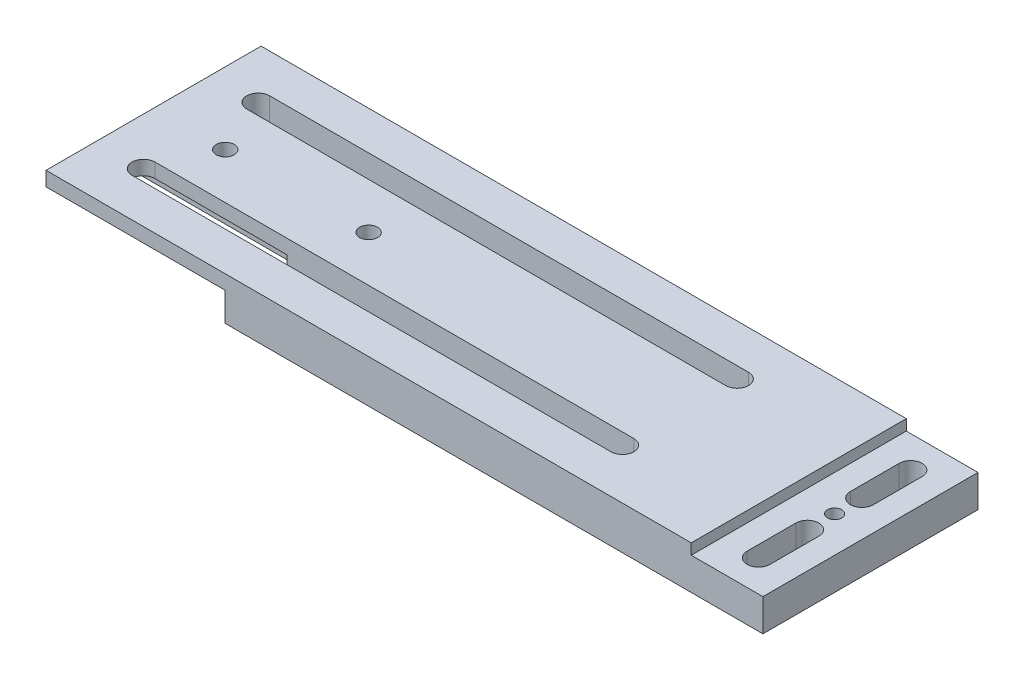
SolidWorks part; units mm, degrees
ref_plane "Front Plane" through (0, 0, 0) normal (0, 0, 1) x (1, 0, 0)
ref_plane "Top Plane" through (0, 0, 0) normal (0, 1, 0) x (1, 0, 0)
ref_plane "Right Plane" through (0, 0, 0) normal (1, 0, 0) x (0, 0, -1)
sketch "Skizze1" plane through (0, 0, 0) normal (0, 1, 0) x (1, 0, 0)
  line L1 (-50, 15) -> (50, 15)
  line L2 (-50, 15) -> (-50, -15)
  line L3 (-50, -15) -> (50, -15)
  line L4 (50, 15) -> (50, -15)
  line L5 (0, -15) -> (0, 15) construction
  line L6 (-50, 0) -> (50, 0) construction
  point P56 (0, 0)
  dimension "D1" = 100
  dimension "D2" = 30
extrude "Aufsatz-Linear austragen1" add sketch "Skizze1" along normal blind 6
hole_wizard "Durchgangsloch für M31" positions "Skizze2" profile "Skizze4" size "M3" standard "DIN" slot yes end condition through all
sketch "Skizze2" plane through (0, 6, 0) normal (0, 1, 0) x (1, 0, 0)
  line L0 (-50, 0) -> (50, 0) construction
  line L1 (-50, 15) -> (-50, -15) construction
  line L2 (50, -15) -> (50, 15) construction
  line L6 (-45, 8) -> (25, 8) construction
  point P0 (-10, 8)
  point P11 (-10, -8)
  dimension "D1" = 16
  dimension "D2" = 70
  dimension "D3" = 60
sketch "Skizze4" plane through (-10, 6, -8) normal (1, 0, 0) x (0, 0, 1)
  line L0 (0, 0) -> (0, 6)
  line L1 (0, 6) -> (1.6, 6)
  line L2 (1.6, 6) -> (1.6, 0)
  line L5 (1.6, 0) -> (0, 0)
  line L11 (0, -6.35) -> (0, 107.95) construction
  dimension "Bohrerdurchmesser" = 3.2
  dimension "Bohrungstiefe" = 6
hole_wizard "Durchgangsloch für M32" positions "Skizze6" profile "Skizze7" size "M3" standard "DIN" slot yes
sketch "Skizze6" plane through (0, 0, 0) normal (0, -1, 0) x (-1, 0, 0)
  line L0 (50, 0) -> (-50, 0) construction
  line L1 (50, 15) -> (50, -15) construction
  line L2 (-50, -15) -> (-50, 15) construction
  line L4 (-45, -7.2051) -> (-45, 7.2051) construction
  line L7 (-45, -12.2051) -> (-45, -2.2051) construction
  point P0 (-45, -7.2051)
  point P17 (-45, 7.2051)
  dimension "D1" = 10
  dimension "D2" = 5
sketch "Skizze7" plane through (45, 0, 7.2051) normal (1, 0, 0) x (0, 0, -1)
  line L0 (0, 0) -> (0, 9.4614)
  line L1 (0, 9.4614) -> (1.6, 8.5)
  line L2 (1.6, 8.5) -> (1.6, 0)
  line L5 (1.6, 0) -> (0, 0)
  line L10 (0, 9.4614) -> (-1.6, 8.5) construction
  line L11 (0, -6.35) -> (0, 107.95) construction
  dimension "Bohrerdurchmesser" = 3.2
  dimension "Bohrungstiefe" = 8.5
  dimension "Spitzenwinkel" = 118
hole_wizard "M3 Gewindebohrung1" positions "Skizze10" profile "Skizze11" tap size "M3" standard "DIN" end condition up to next
sketch "Skizze10" plane through (0, 6, 0) normal (0, 1, 0) x (1, 0, 0)
  line L0 (-50, 15) -> (-50, -15) construction
  line L1 (-50, 0) -> (50, 0) construction
  line L2 (50, -15) -> (50, 15) construction
  point P0 (-40, 0)
  point P11 (-20, 0)
  dimension "D1" = 10
  dimension "D2" = 20
sketch "Skizze11" plane through (-40, 6, 0) normal (1, 0, 0) x (0, 0, 1)
  line L0 (0, 0) -> (0, 6)
  line L1 (0, 6) -> (1.25, 6)
  line L2 (1.25, 6) -> (1.25, 0)
  line L5 (1.25, 0) -> (0, 0)
  line L11 (0, -6.35) -> (0, 107.95) construction
  dimension "Bohrerdurchmesser" = 2.5
  dimension "Bohrungstiefe" = 6
cosmetic thread "Bohrungsgewinde1" parameters "D2"=3
cosmetic thread "Bohrungsgewinde2" parameters "D2"=3
sketch "Skizze12" plane through (-50, 0, 0) normal (-1, 0, 0) x (0, 0, 1)
  line L1 (15, 0) -> (3, 0)
  line L2 (15, 0) -> (15, 4)
  line L3 (15, 4) -> (3, 4)
  line L4 (3, 0) -> (3, 4)
  line L5 (9, 4) -> (9, 0) construction
  line L6 (15, 2) -> (3, 2) construction
  point P64 (9, 2)
  dimension "D1" = 4
  dimension "D2" = 12
extrude "Schnitt-Linear austragen1" cut sketch "Skizze12" against normal blind 25
fillet "Verrundung1" radius 2.5 1 edges at (-25, 2, 3)
sketch "Skizze13" plane through (0, 6, 0) normal (0, 1, 0) x (1, 0, 0)
  line L0 (50, 15) -> (-50, 15) construction
  line L1 (50, -15) -> (40, -15)
  line L2 (50, -15) -> (50, 15)
  line L3 (50, 15) -> (40, 15)
  line L4 (40, -15) -> (40, 15)
  line L5 (45, 15) -> (45, -15) construction
  line L6 (50, 0) -> (40, 0) construction
  point P140 (45, 0)
  dimension "D1" = 10
extrude "Schnitt-Linear austragen2" cut sketch "Skizze13" against normal blind 1.5
hole_wizard "Ø2.0mm Stiftloch1" positions "Skizze16" profile "Skizze17" hole size "Ø2.0" standard "DIN"
sketch "Skizze16" plane through (0, 4.5, 0) normal (0, 1, 0) x (1, 0, 0)
  line L0 (45, 2.2051) -> (45, -2.2051) construction
  arc A0 (43.4, 3.8051) -> (46.6, 3.8051) centre (45, 3.8051) ccw construction
  arc A1 (46.6, -3.8051) -> (43.4, -3.8051) centre (45, -3.8051) ccw construction
  point P0 (45, 0)
sketch "Skizze17" plane through (45, 4.5, 0) normal (1, 0, 0) x (0, 0, 1)
  line L0 (0, 0) -> (0, 9.1009)
  line L1 (0, 9.1009) -> (1, 8.5)
  line L2 (1, 8.5) -> (1, 0)
  line L5 (1, 0) -> (0, 0)
  line L10 (0, 9.1009) -> (-1, 8.5) construction
  line L11 (0, -6.35) -> (0, 107.95) construction
  dimension "Bohrerdurchmesser" = 2
  dimension "Bohrungstiefe" = 8.5
  dimension "Spitzenwinkel" = 118
